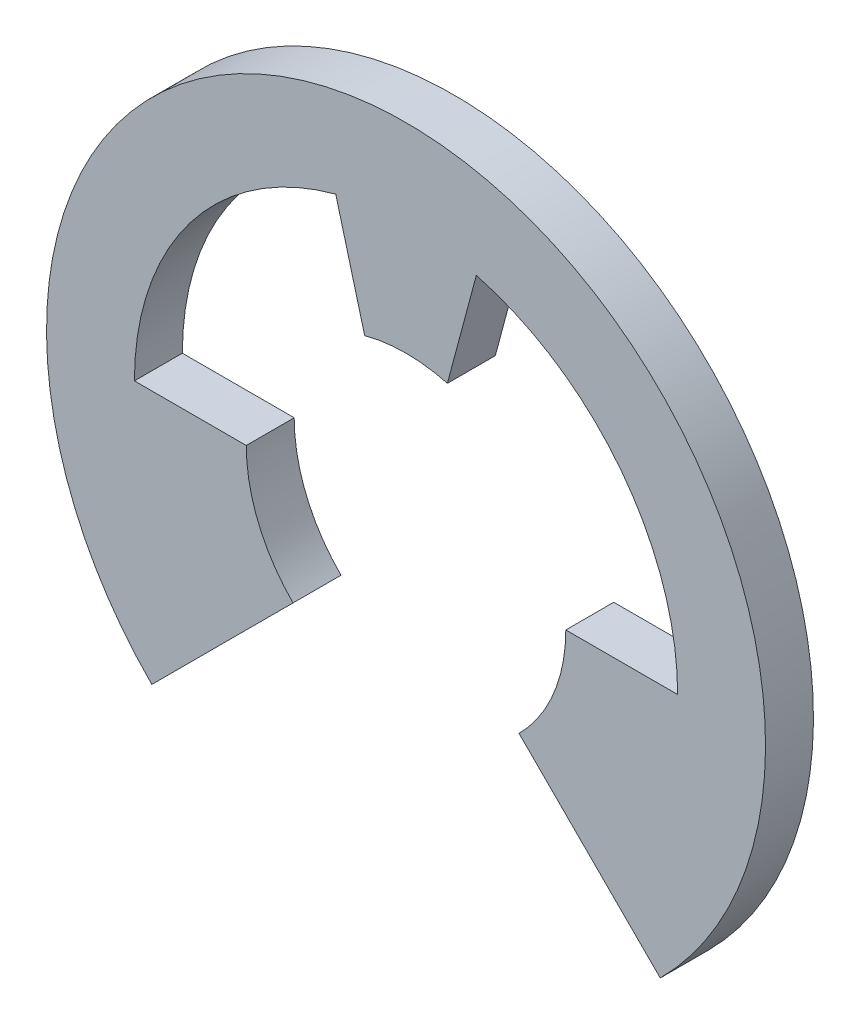
SolidWorks part; units mm, degrees
material "不锈钢 (铁素体)"
ref_plane "前视基准面" through (0, 0, 0) normal (0, 0, 1) x (1, 0, 0)
ref_plane "上视基准面" through (0, 0, 0) normal (0, 1, 0) x (1, 0, 0)
ref_plane "右视基准面" through (0, 0, 0) normal (1, 0, 0) x (0, 0, -1)
ref_plane "基准面4" through (0, 0, 0.6) normal (0, 0, 1) x (1, 0, 0)
sketch "草图1" plane through (0, 0, 0.6) normal (0, 0, 1) x (1, 0, 0)
  line L0 (1.4142, -1.4142) -> (3.182, -3.182)
  line L1 (-3.182, -3.182) -> (-1.4142, -1.4142)
  line L2 (-2, 0) -> (-3.4, 0)
  line L3 (-0.88, 3.2841) -> (-0.5176, 1.9319)
  line L4 (0.5176, 1.9319) -> (0.88, 3.2841)
  line L5 (3.4, 0) -> (2, 0)
  arc A0 (3.182, -3.182) -> (-3.182, -3.182) centre (0, 0) ccw
  arc A1 (-1.4142, -1.4142) -> (-2, 0) centre (0, 0) cw
  arc A2 (-3.4, 0) -> (-0.88, 3.2841) centre (0, 0) cw
  arc A3 (-0.5176, 1.9319) -> (0.5176, 1.9319) centre (0, 0) cw
  arc A4 (0.88, 3.2841) -> (3.4, 0) centre (0, 0) cw
  arc A5 (2, 0) -> (1.4142, -1.4142) centre (0, 0) cw
extrude "凸台-拉伸1" add sketch "草图1" against normal blind 0.6
